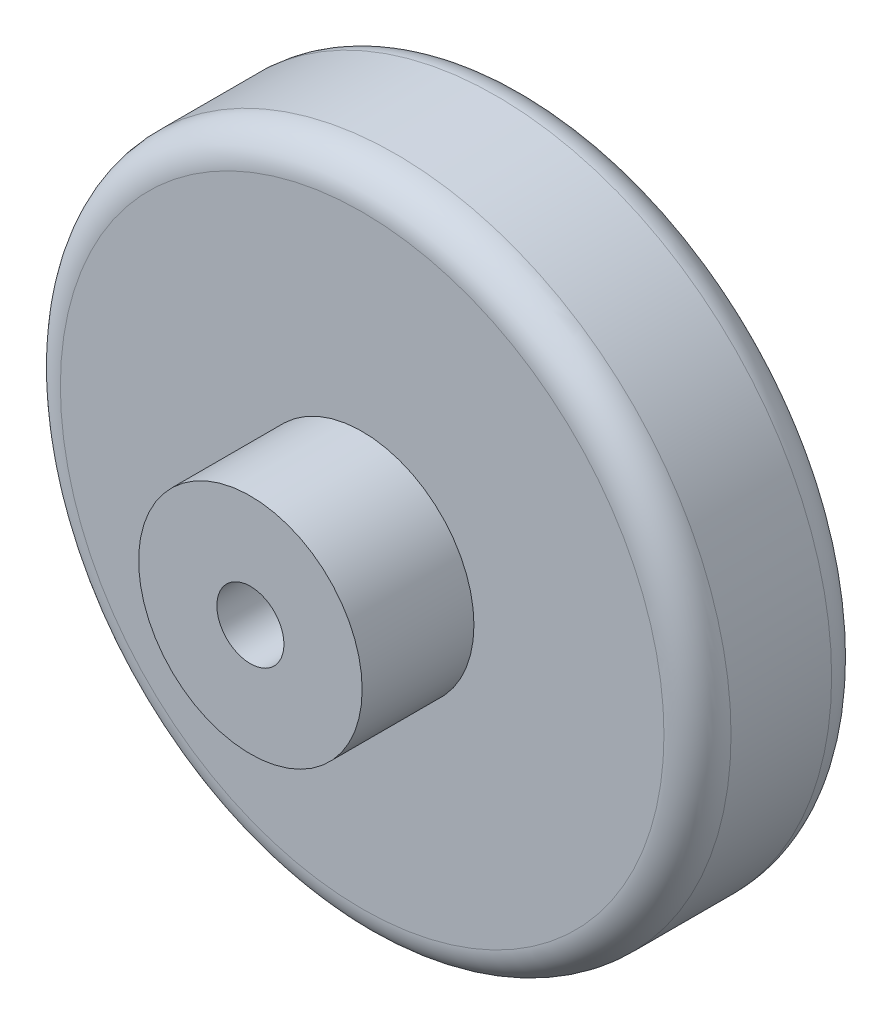
SolidWorks part; units mm, degrees
ref_plane "Front Plane" through (0, 0, 0) normal (0, 0, 1) x (1, 0, 0)
ref_plane "Top Plane" through (0, 0, 0) normal (0, 1, 0) x (1, 0, 0)
ref_plane "Right Plane" through (0, 0, 0) normal (1, 0, 0) x (0, 0, -1)
sketch "Sketch1" plane through (0, 0, 0) normal (0, 0, 1) x (1, 0, 0)
  circle A0 centre (0, 0) radius 30
  dimension "D1" = 60
extrude "Boss-Extrude1" add sketch "Sketch1" along normal blind 15
sketch "Sketch2" plane through (0, 0, 15) normal (0, 0, 1) x (1, 0, 0)
  circle A0 centre (0, 0) radius 10
  dimension "D1" = 20
extrude "Boss-Extrude2" add sketch "Sketch2" along normal blind 10
sketch "Sketch3" plane through (0, 0, 25) normal (0, 0, 1) x (1, 0, 0)
  circle A0 centre (0, 0) radius 3
  dimension "D1" = 6
extrude "Cut-Extrude1" cut sketch "Sketch3" against normal through all
fillet "Fillet1" radius 3 2 edges at (30, 0, 0) (30, 0, 15)
sketch "Sketch4" plane through (0, 0, 0) normal (0, 0, -1) x (-1, 0, 0)
  circle A0 centre (0, 0) radius 6
  dimension "D1" = 12
extrude "Cut-Extrude2" cut sketch "Sketch4" against normal blind 4
fillet "Fillet2" radius 1 1 edges at (-6, 0, 0)
